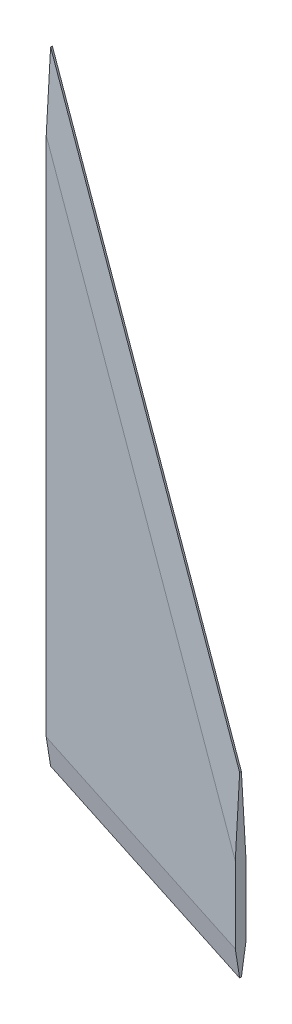
SolidWorks part; units mm, degrees
material "6061 Alloy"
ref_plane "Front Plane" through (0, 0, 0) normal (0, 0, 1) x (1, 0, 0)
ref_plane "Top Plane" through (0, 0, 0) normal (0, 1, 0) x (1, 0, 0)
ref_plane "Right Plane" through (0, 0, 0) normal (1, 0, 0) x (0, 0, -1)
sketch "Sketch1" plane through (0, 0, 0) normal (0, 0, 1) x (1, 0, 0)
  line L0 (-16.41, -60.6992) -> (-16.41, 117.1008)
  line L1 (-16.41, 117.1008) -> (37.565, -35.2992)
  line L2 (37.565, -35.2992) -> (37.565, -86.0992)
  line L3 (37.565, -86.0992) -> (-16.41, -60.6992)
extrude "Boss-Extrude1" add sketch "Sketch1" along normal mid plane 3
chamfer "Chamfer1" distance 1.25 angle 80 4 edges at (10.5775, -73.3992, -1.5) (10.5775, -73.3992, 1.5) (10.5775, 40.9008, -1.5) (10.5775, 40.9008, 1.5) first distance on face at (10.5775, -73.3992, 0) first distance on face at (10.5775, 40.9008, 0)
